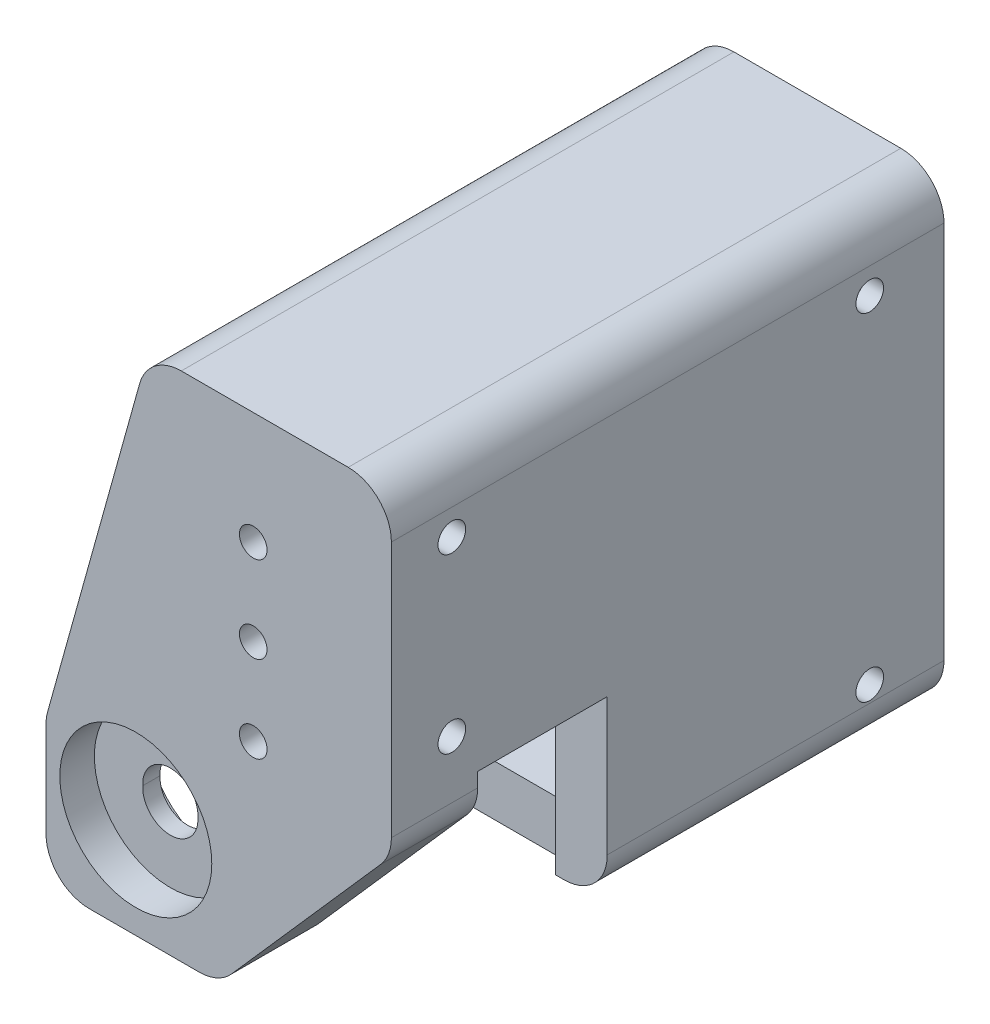
SolidWorks part; units mm, degrees
ref_plane "Front Plane" through (0, 0, 0) normal (0, 0, 1) x (1, 0, 0)
ref_plane "Top Plane" through (0, 0, 0) normal (0, 1, 0) x (1, 0, 0)
ref_plane "Right Plane" through (0, 0, 0) normal (1, 0, 0) x (0, 0, -1)
sketch "Sketch1" plane through (0, 0, 0) normal (0, 0, 1) x (1, 0, 0)
  line L1 (-1.5468, -4.5791) -> (49.2532, -4.5791)
  line L2 (-1.5468, -4.5791) -> (-1.5468, -80.7791)
  line L3 (-1.5468, -80.7791) -> (49.2532, -80.7791)
  line L4 (49.2532, -4.5791) -> (49.2532, -80.7791)
  dimension "D1" = 50.8
  dimension "D2" = 76.2
extrude "Boss-Extrude1" add sketch "Sketch1" along normal blind 12.7
sketch "Sketch3" plane through (0, 0, 12.7) normal (0, 0, 1) x (1, 0, 0)
  line L0 (49.2532, -80.7791) -> (49.2532, -4.5791) construction
  line L1 (49.2532, -4.5791) -> (-1.5468, -4.5791) construction
  line L2 (28.9332, -4.5791) -> (28.9332, -80.7791) construction
  line L4 (-1.5468, -80.7791) -> (49.2532, -80.7791) construction
  circle A0 centre (28.9332, -42.6791) radius 2.032
  circle A1 centre (28.9332, -29.9791) radius 2.032
  circle A2 centre (28.9332, -17.2791) radius 2.032
  dimension "D1" = 12.7
  dimension "D2" = 4.064
  dimension "D3" = 4.064
  dimension "D4" = 4.064
  dimension "D9" = 12.7
  dimension "D5" = 0
  dimension "D6" = 12.7
  dimension "D7" = 20.32
  dimension "D8" = 0
extrude "Cut-Extrude1" cut sketch "Sketch3" against normal blind 12.7
sketch "Sketch4" plane through (0, 0, 12.7) normal (0, 0, 1) x (1, 0, 0)
  circle A1 centre (11.6612, -61.3027) radius 4.064
  circle A4 centre (28.9332, -42.6791) radius 2.032 construction
  dimension "D1" = 25.4
  dimension "D2" = 8.128
  dimension "D3" = 17.272
sketch "Sketch17" plane through (0, 0, 0) normal (0, 0, -1) x (-1, 0, 0)
  line L0 (1.5468, -80.7791) -> (-49.2532, -80.7791) construction
  line L1 (-49.2532, -4.5791) -> (-41.6332, -4.5791)
  line L2 (-49.2532, -4.5791) -> (-49.2532, -80.7791)
  line L3 (-49.2532, -80.7791) -> (-41.6332, -80.7791)
  line L4 (-41.6332, -4.5791) -> (-41.6332, -80.7791)
  dimension "D1" = 7.62
extrude "Boss-Extrude13" add sketch "Sketch17" along normal blind 68.58
sketch "Sketch18" plane through (41.6332, 0, 0) normal (-1, 0, 0) x (0, 0, 1)
  line L1 (-68.58, -80.7791) -> (-64.77, -80.7791)
  line L2 (-68.58, -80.7791) -> (-68.58, -61.7291)
  line L3 (-68.58, -61.7291) -> (-64.77, -61.7291)
  line L4 (-64.77, -80.7791) -> (-64.77, -61.7291)
  dimension "D1" = 19.05
  dimension "D2" = 3.81
extrude "Boss-Extrude14" add sketch "Sketch18" along normal blind 43.18
sketch "Sketch19" plane through (41.6332, 0, 0) normal (-1, 0, 0) x (0, 0, 1)
  line L0 (-64.77, -80.7791) -> (0, -80.7791) construction
  line L1 (-21.59, -80.7791) -> (-50.8, -80.7791)
  line L2 (-21.59, -80.7791) -> (-21.59, -61.7291)
  line L3 (-21.59, -61.7291) -> (-50.8, -61.7291)
  line L4 (-50.8, -80.7791) -> (-50.8, -61.7291)
  line L5 (-64.77, -80.7791) -> (-64.77, -61.7291) construction
  dimension "D1" = 13.97
  dimension "D2" = 29.21
  dimension "D3" = 19.05
extrude "Boss-Extrude15" add sketch "Sketch19" along normal blind 43.18
extrude "Cut-Extrude5" cut sketch "Sketch4" against normal through all contours A1
sketch "Sketch21" plane through (0, 0, 0) normal (0, 0, -1) x (-1, 0, 0)
  circle A0 centre (-11.6612, -61.3027) radius 11.176
  circle A1 centre (-11.6612, -61.3027) radius 4.064
  dimension "D1" = 22.352
  dimension "D2" = 8.128
extrude "Cut-Extrude6" cut sketch "Sketch21" against normal blind 5.08
sketch "Sketch22" plane through (0, 0, 12.7) normal (0, 0, 1) x (1, 0, 0)
  circle A0 centre (11.6612, -61.3027) radius 11.176
  circle A1 centre (11.6612, -61.3027) radius 4.064
  dimension "D1" = 22.352
  dimension "D2" = 8.128
extrude "Cut-Extrude7" cut sketch "Sketch22" against normal blind 5.08
sketch "Sketch23" plane through (41.6332, 0, 0) normal (-1, 0, 0) x (0, 0, 1)
  line L1 (0, -80.7791) -> (-19.05, -80.7791)
  line L2 (0, -80.7791) -> (0, -42.6791)
  line L3 (0, -42.6791) -> (-19.05, -42.6791)
  line L4 (-19.05, -80.7791) -> (-19.05, -42.6791)
  dimension "D1" = 38.1
  dimension "D2" = 19.05
extrude "Cut-Extrude8" cut sketch "Sketch23" against normal through all
sketch "Sketch24" plane through (0, -80.7791, 0) normal (0, -1, 0) x (1, 0, 0)
  line L0 (49.2532, -19.05) -> (49.2532, -68.58) construction
  line L1 (0.9932, -24.0843) -> (45.4432, -24.0843)
  line L2 (0.9932, -24.0843) -> (0.9932, -49.5327)
  line L3 (0.9932, -49.5327) -> (45.4432, -49.5327)
  line L4 (45.4432, -24.0843) -> (45.4432, -49.5327)
  dimension "D1" = 3.81
  dimension "D2" = 44.45
sketch "Sketch26" plane through (0, -61.7291, 0) normal (0, 1, 0) x (1, 0, 0)
  line L8 (15.7027, 21.59) -> (41.6332, 21.59) construction
  line L9 (-1.5468, 68.58) -> (16.2332, 68.58)
  line L10 (-1.5468, 68.58) -> (-1.5468, 21.59)
  line L11 (-1.5468, 21.59) -> (16.2332, 21.59)
  line L12 (16.2332, 68.58) -> (16.2332, 21.59)
  line L13 (41.6332, 68.58) -> (41.6332, 0) construction
  dimension "D1" = 25.4
extrude "Boss-Extrude16" add sketch "Sketch26" along normal blind 57.15
sketch "Sketch28" plane through (0, -4.5791, 0) normal (0, 1, 0) x (1, 0, 0)
  line L5 (-1.5468, 68.58) -> (49.2532, 68.58)
  line L6 (-1.5468, 68.58) -> (-1.5468, -12.7)
  line L7 (-1.5468, -12.7) -> (49.2532, -12.7)
  line L8 (49.2532, 68.58) -> (49.2532, -12.7)
extrude "Boss-Extrude18" add sketch "Sketch28" along normal blind 3.81
sketch "Sketch32" plane through (49.2532, 0, 0) normal (1, 0, 0) x (0, 0, -1)
  line L0 (68.58, -0.7691) -> (68.58, -80.7791) construction
  line L1 (19.05, -80.7791) -> (68.58, -80.7791) construction
  line L4 (-12.7, -0.7691) -> (68.58, -0.7691) construction
  line L6 (-12.7, -80.7791) -> (-12.7, -0.7691) construction
  circle A0 centre (-3.81, -36.3291) radius 2.032
  circle A1 centre (57.785, -10.9291) radius 2.032
  circle A2 centre (57.785, -60.4591) radius 2.032
  circle A3 centre (-3.81, -10.9291) radius 2.032
  dimension "D1" = 4.064
  dimension "D2" = 4.064
  dimension "D3" = 4.064
  dimension "D4" = 4.064
  dimension "D5" = 10.795
  dimension "D6" = 20.32
  dimension "D7" = 10.795
  dimension "D9" = 8.89
  dimension "D10" = 25.4
  dimension "D12" = 0
  dimension "D8" = 10.16
  dimension "D11" = 8.89
sketch "Sketch35" plane through (0, 0, 12.7) normal (0, 0, 1) x (1, 0, 0)
  line L0 (7.6196, -61.7291) -> (15.7027, -61.7291) construction
  circle A0 centre (11.6612, -61.7291) radius 4.064
  dimension "D1" = 8.128
extrude "Cut-Extrude10" cut sketch "Sketch35" against normal through all
extrude "Cut-Extrude12" cut sketch "Sketch32" against normal blind 9.525 contours A0 | A3
sketch "Sketch37" plane through (49.2532, 0, 0) normal (1, 0, 0) x (0, 0, -1)
  line L1 (68.58, -0.7691) -> (68.58, -80.7791) construction
  line L2 (-12.7, -0.7691) -> (68.58, -0.7691) construction
  line L3 (19.05, -80.7791) -> (68.58, -80.7791) construction
  circle A0 centre (57.658, -10.9291) radius 2.032
  circle A1 centre (57.658, -60.4591) radius 2.032
  dimension "D1" = 4.064
  dimension "D2" = 10.922
  dimension "D4" = 4.064
  dimension "D5" = 20.32
  dimension "D6" = 10.922
  dimension "D3" = 10.16
sketch "Sketch41" plane through (41.6332, 0, 0) normal (-1, 0, 0) x (0, 0, 1)
  circle A0 centre (-57.658, -10.9291) radius 2.032
  circle A1 centre (-57.658, -60.4591) radius 2.032
  point P0 (-57.658, -10.9291)
  point P3 (-57.658, -60.4591)
extrude "Cut-Extrude14" cut sketch "Sketch41" against normal blind 9.525
sketch "Sketch43" plane through (41.6332, 0, 0) normal (-1, 0, 0) x (0, 0, 1)
  circle A0 centre (-57.658, -10.9291) radius 3.9687
  circle A1 centre (-57.658, -60.4591) radius 3.9687
  dimension "D1" = 7.9375
  dimension "D2" = 7.9375
extrude "Cut-Extrude15" cut sketch "Sketch43" against normal blind 4.7625
sketch "Sketch45" plane through (0, 0, 12.7) normal (0, 0, 1) x (1, 0, 0)
  circle A0 centre (28.9332, -42.6791) radius 3.937
  dimension "D1" = 7.874
sketch "Sketch46" plane through (0, 0, 0) normal (0, 0, -1) x (-1, 0, 0)
  circle A0 centre (-28.9332, -42.6791) radius 3.937
  dimension "D1" = 7.874
extrude "Cut-Extrude17" cut sketch "Sketch46" against normal blind 3.048
sketch "Sketch48" plane through (-1.5468, 0, 0) normal (-1, 0, 0) x (0, 0, 1)
  circle A0 centre (-57.658, -10.9291) radius 2.54
  dimension "D1" = 5.08
extrude "Cut-Extrude18" cut sketch "Sketch48" against normal blind 25.908
sketch "Sketch49" plane through (0, 0, 12.7) normal (0, 0, 1) x (1, 0, 0)
  line L0 (49.2532, -80.7791) -> (49.2532, -0.7691) construction
  line L1 (-1.5468, -80.7791) -> (49.2532, -80.7791)
  line L2 (-1.5468, -80.7791) -> (-1.5468, -76.0343)
  line L3 (-1.5468, -76.0343) -> (49.2532, -76.0343)
  line L4 (49.2532, -80.7791) -> (49.2532, -76.0343)
extrude "Cut-Extrude19" cut sketch "Sketch49" against normal blind 92.202
sketch "Sketch51" plane through (0, 0, 12.7) normal (0, 0, 1) x (1, 0, 0)
  line L0 (13.5307, -0.7691) -> (-1.5468, -54.8696)
  line L1 (-1.5468, -0.7691) -> (49.2532, -0.7691) construction
  line L2 (-1.5468, -0.7691) -> (-1.5468, -76.0343) construction
  line L3 (-1.5468, -54.8696) -> (-1.5468, -0.7691)
  line L4 (-1.5468, -0.7691) -> (13.5307, -0.7691)
extrude "Cut-Extrude20" cut sketch "Sketch51" against normal blind 92.202
sketch "Sketch52" plane through (0, 0, -68.58) normal (0, 0, -1) x (-1, 0, 0)
  line L0 (1.5468, -54.8696) -> (1.5468, -76.0343) construction
  line L1 (-49.2532, -76.0343) -> (1.5468, -76.0343)
  line L2 (-49.2532, -76.0343) -> (-49.2532, -69.1896)
  line L3 (-49.2532, -69.1896) -> (1.5468, -69.1896)
  line L4 (1.5468, -76.0343) -> (1.5468, -69.1896)
extrude "Cut-Extrude21" cut sketch "Sketch52" against normal blind 62.484
sketch "Sketch53" plane through (0, 0, 12.7) normal (0, 0, 1) x (1, 0, 0)
  line L0 (23.8532, -76.0343) -> (49.2532, -47.1752)
  line L1 (49.2532, -76.0343) -> (-1.5468, -76.0343) construction
  line L2 (49.2532, -76.0343) -> (49.2532, -0.7691) construction
  line L3 (49.2532, -47.1752) -> (49.2532, -76.0343)
  line L4 (49.2532, -76.0343) -> (23.8532, -76.0343)
extrude "Cut-Extrude22" cut sketch "Sketch53" against normal blind 23.876
fillet "Fillet1" radius 6.35 1 edges at (-1.5468, -54.8696, -45.085)
fillet "Fillet2" radius 6.35 1 edges at (13.5307, -0.7691, -27.94)
fillet "Fillet3" radius 6.35 1 edges at (-1.5468, -54.8696, 6.35)
fillet "Fillet4" radius 6.35 1 edges at (49.2532, -0.7691, -27.94)
fillet "Fillet5" radius 6.35 1 edges at (49.2532, -47.1752, 6.35)
fillet "Fillet6" radius 6.35 2 edges at (23.8532, -76.0343, 6.35) (-1.5468, -76.0343, 6.35)
fillet "Fillet7" radius 6.35 2 edges at (-1.5468, -69.1896, -66.675) (-1.5468, -69.1896, -36.195)
fillet "Fillet8" radius 6.35 1 edges at (49.2532, -69.1896, -43.815)
